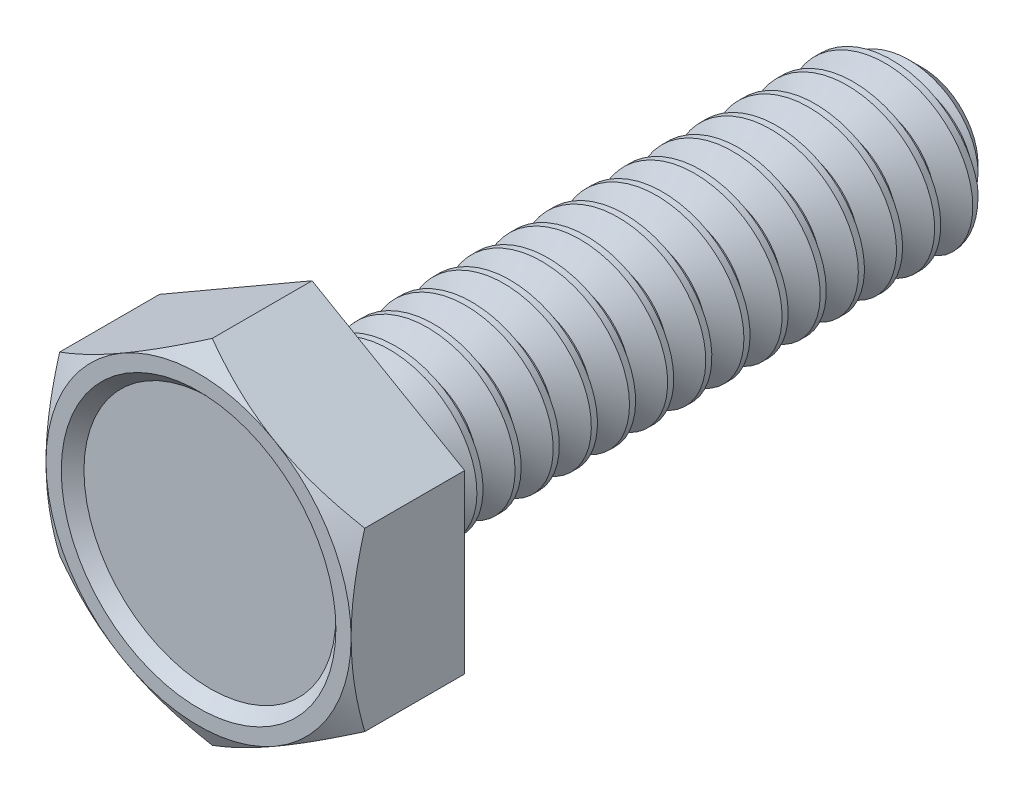
SolidWorks part; units mm, degrees
ref_plane "Front" through (0, 0, 0) normal (0, 0, 1) x (1, 0, 0)
ref_plane "Top" through (0, 0, 0) normal (0, 1, 0) x (1, 0, 0)
ref_plane "Right" through (0, 0, 0) normal (1, 0, 0) x (0, 0, -1)
sketch "Sketch1" plane through (0, 0, 0) normal (0, 0, 1) x (1, 0, 0)
  line L1 (-3.175, -1.8331) -> (0, -3.6662)
  line L2 (0, -3.6662) -> (3.175, -1.8331)
  line L3 (3.175, -1.8331) -> (3.175, 1.8331)
  line L4 (3.175, 1.8331) -> (0, 3.6662)
  line L5 (0, 3.6662) -> (-3.175, 1.8331)
  line L6 (-3.175, 1.8331) -> (-3.175, -1.8331)
  circle A0 centre (0, 0) radius 3.175 construction
  circle A1 centre (0, 0) radius 3.175 construction
  dimension "Head Dia" = 6.35
extrude "Extrude3" add sketch "Sketch1" along normal blind 2.3622
sketch "Sketch4" plane through (0, 0, 0) normal (1, 0, 0) x (0, 0, -1)
  line L0 (0, 0) -> (12.7, 0)
  line L3 (12.7, 0) -> (12.7, 1.7526)
  line L4 (12.7, 1.7526) -> (0, 1.7526)
  line L6 (0, 1.7526) -> (0, 0)
  line L9 (12.7, 1.7526) -> (12.7, -1.7526) construction
  dimension "length" = 12.7
  dimension "dia" = 3.5052
revolve "Revolve1" add sketch "Sketch4" angle 360 about L0
sketch "Sketch13" plane through (0, 0, -12.7) normal (0, 0, -1) x (-1, 0, 0)
  circle A2 centre (0, 0) radius 1.7526
curve "Helix/Spiral1" pitch 0.7937 height 15.0622 radius 1.7526 centre (0, 0, -12.7) axis (0, 0, 1) start towards (1, 0, 0)
chamfer "Chamfer2" distance 0.5953 angle 45 1 edges at (1.7526, 0, -12.7)
sketch "Sketch14" plane through (0, 0, 0) normal (1, 0, 0) x (0, 0, -1)
  line L0 (12.7, 1.7774) -> (13.3945, 1.7774)
  line L1 (13.3945, 1.7774) -> (13.0969, 1.2404)
  line L2 (13.0969, 1.2404) -> (12.9977, 1.2404)
  line L3 (12.9977, 1.2404) -> (12.7, 1.7774)
  line L4 (12.8488, 1.5089) -> (13.2457, 1.5089) construction
  dimension "D1" = 0.0992
  dimension "D2" = 58
  dimension "D3" = 0.3969
  dimension "D4" = 0.0248
sweep "Cut-Sweep1" cut profiles "Sketch14" path "Helix/Spiral1" align with end faces yes
ref_plane "Plane1" through (0, 0, 25.4) normal (0, 0, -1) x (-1, 0, 0)
sketch "Sketch29" [suppressed] plane through (0, 0, 28.575) normal (0, 0, -1) x (-1, 0, 0)
  circle A0 centre (0, 0) radius 1.7526 construction
  circle A1 centre (0, 0) radius 1.7526
  point P3 (0, -1.7526)
  point P4 (0, 1.7526)
extrude "Extrude11" [suppressed] add sketch "Sketch29" against normal up to surface (28.575 mm away) up to plane "Front"
sketch "Sketch26" plane through (0, 0, 0) normal (0, 0, 1) x (1, 0, 0)
  circle A1 centre (0, 0) radius 0.5461
  dimension "D1" = 1.0922
extrude "Extrude12" add sketch "Sketch26" along normal up to surface (2.3622 mm away) up to face at (0, 0, 2.3622)
sketch "Sketch30" plane through (0, 0, 2.3622) normal (0, 0, 1) x (1, 0, 0)
  circle A0 centre (0, 0) radius 3.175 construction
  circle A1 centre (0, 0) radius 3.175
extrude "Extrude13" cut sketch "Sketch30" against normal blind 2.54 draft 60 flip side to cut
sketch "Sketch31" plane through (0, 0, 2.3622) normal (0, 0, 1) x (1, 0, 0)
  circle A0 centre (0, 0) radius 2.8575
  dimension "D1" = 5.715
extrude "Extrude14" cut sketch "Sketch31" against normal blind 0.2362 draft 45
sketch "Sketch18" plane through (0, 0, 0) normal (1, 0, 0) x (0, 0, -1)
  line L1 (12.7, 1.7526) -> (0, 1.7526) construction
  line L2 (-2.3622, 3.175) -> (-2.3622, 2.7496) construction
  point P0 (11.5094, -1.7526)
  point P1 (11.9062, 1.7526)
  point P2 (-2.3622, 3.6662)
  dimension "D1" = 0.7937
  dimension "D2" = 1.1906
equation "\"D3@Helix/Spiral1\" = \"length@Sketch4\" + \"Head Ht@Extrude3\""
equation "\"D1@Sketch14\" = \"D4@Helix/Spiral1\" * .125"
equation "\"D3@Sketch14\" = \"D4@Helix/Spiral1\" * .5"
equation "\"D4@Sketch14\" = \"D1@Sketch14\" * .25"
equation "\"D1@Chamfer2\" = \"D4@Helix/Spiral1\" * .75"
equation "\"D1@Sketch18\" = \"D4@Helix/Spiral1\""
equation "\"D2@Sketch18\" = \"D4@Helix/Spiral1\" * 1.5"
equation "\"D1@Sketch31\" = \"Head Dia@Sketch1\" * .9"
equation "\"D1@Extrude14\" = \"Head Ht@Extrude3\" * .1"
